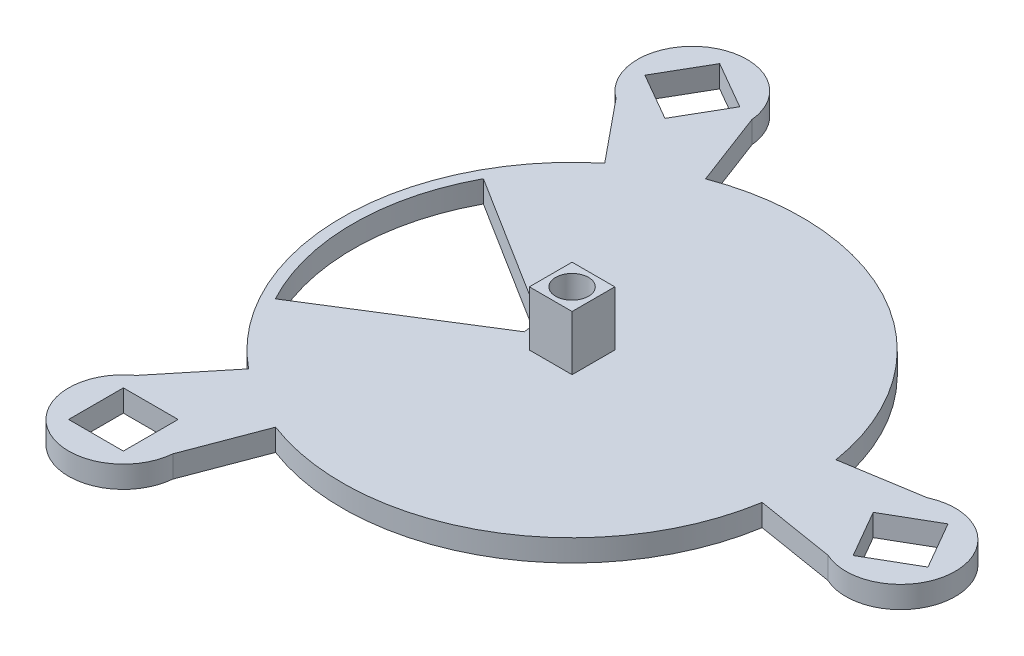
SolidWorks part; units mm, degrees
ref_plane "Front Plane" through (0, 0, 0) normal (0, 0, 1) x (1, 0, 0)
ref_plane "Top Plane" through (0, 0, 0) normal (0, 1, 0) x (1, 0, 0)
ref_plane "Right Plane" through (0, 0, 0) normal (1, 0, 0) x (0, 0, -1)
sketch "Sketch1" plane through (0, 0, 0) normal (0, 1, 0) x (1, 0, 0)
  line L0 (0, 0) -> (-15, -25.9808) construction
  line L4 (-17.5, -23.4808) -> (-12.5, -23.4808)
  line L5 (-17.5, -23.4808) -> (-17.5, -28.4808)
  line L6 (-17.5, -28.4808) -> (-12.5, -28.4808)
  line L7 (-12.5, -23.4808) -> (-12.5, -28.4808)
  line L8 (0, 0) -> (-17.8866, -21.8982)
  line L15 (0, 0) -> (-10.0211, -26.4394)
  line L16 (-11.5849, 26.8958) -> (-14.0849, 22.5657)
  line L17 (-11.5849, 26.8958) -> (-15.9151, 29.3958)
  line L18 (-15.9151, 29.3958) -> (-18.4151, 25.0657)
  line L19 (-14.0849, 22.5657) -> (-18.4151, 25.0657)
  line L20 (0, 0) -> (-10.0211, 26.4394)
  line L21 (0, 0) -> (-15, 25.9808) construction
  line L22 (0, 0) -> (-17.8866, 21.8982)
  line L23 (29.0849, -3.4151) -> (26.5849, 0.9151)
  line L24 (29.0849, -3.4151) -> (33.4151, -0.9151)
  line L25 (33.4151, -0.9151) -> (30.9151, 3.4151)
  line L26 (26.5849, 0.9151) -> (30.9151, 3.4151)
  line L27 (0, 0) -> (27.9077, -4.5412)
  line L28 (0, 0) -> (30, 0) construction
  line L29 (0, 0) -> (27.9077, 4.5412)
  line L30 (0, 0) -> (0, -21) construction
  circle A0 centre (0, 0) radius 21
  arc A1 (-17.8866, -21.8982) -> (-10.0211, -26.4394) centre (-15, -25.9808) ccw
  arc A2 (-10.0211, 26.4394) -> (-17.8866, 21.8982) centre (-15, 25.9808) ccw
  arc A3 (27.9077, -4.5412) -> (27.9077, 4.5412) centre (30, 0) ccw
  point P8 (-15, -28.4808)
  point P9 (-17.5, -25.9808)
  point P29 (0, 0)
  dimension "D1" = 42
  dimension "D5" = 5
  dimension "D2" = 30
  dimension "D3" = 5
  dimension "D4" = 28.2748
  dimension "D6" = 3
  dimension "D7" = 120
  dimension "D8" = 120
  dimension "D9" = 120
  dimension "D10" = 30
extrude "Boss-Extrude1" add sketch "Sketch1" along normal blind 2 contours L8 A1 L15 A0 L4 L7 L6 L5 | L27 A3 L29 A0 L23 L26 L25 L24 | L20 A2 L22 A0 L16 L19 L18 L17 | A0 region at (-10.5967, 0, 18.3541) region at (-10.5967, 0, -18.3541) region at (21.1054, 0, 1.7059)
ref_plane "Plane1" through (0, 2, 0) normal (0, 1, 0) x (1, 0, 0)
sketch "Sketch2" plane through (0, 2, 0) normal (0, 1, 0) x (1, 0, 0)
  line L1 (-1.95, 1.95) -> (1.95, 1.95)
  line L2 (-1.95, 1.95) -> (-1.95, -1.95)
  line L3 (-1.95, -1.95) -> (1.95, -1.95)
  line L4 (1.95, 1.95) -> (1.95, -1.95)
  point P4 (0, -1.95)
  point P6 (-1.95, 0)
  dimension "D1" = 3.9
extrude "Boss-Extrude2" add sketch "Sketch2" along normal blind 5
ref_plane "Plane2" through (0, 7, 0) normal (0, 1, 0) x (1, 0, 0)
sketch "Sketch3" plane through (0, 7, 0) normal (0, 1, 0) x (1, 0, 0)
  circle A0 centre (0, 0) radius 1.5
  dimension "D1" = 3
extrude "Cut-Extrude1" cut sketch "Sketch3" against normal up to next
sketch "Sketch4" plane through (0, 2, 0) normal (0, 1, 0) x (1, 0, 0)
  line L0 (0, 0) -> (-20, 0) construction
  line L1 (-3.6203, -0.735) -> (-17.5997, -9.5)
  line L2 (-3.6203, 0.735) -> (-17.5997, 9.5)
  arc A1 (-17.5997, 9.5) -> (-17.5997, -9.5) centre (0, 0) ccw
  arc A2 (-3.6203, 0.735) -> (-3.6203, -0.735) centre (0, 0) ccw
  dimension "D1" = 40
  dimension "D4" = 1.47
  dimension "D2" = 9.5
  dimension "D3" = 9.5
  dimension "D5" = 16.5
extrude "Cut-Extrude2" cut sketch "Sketch4" against normal up to next
